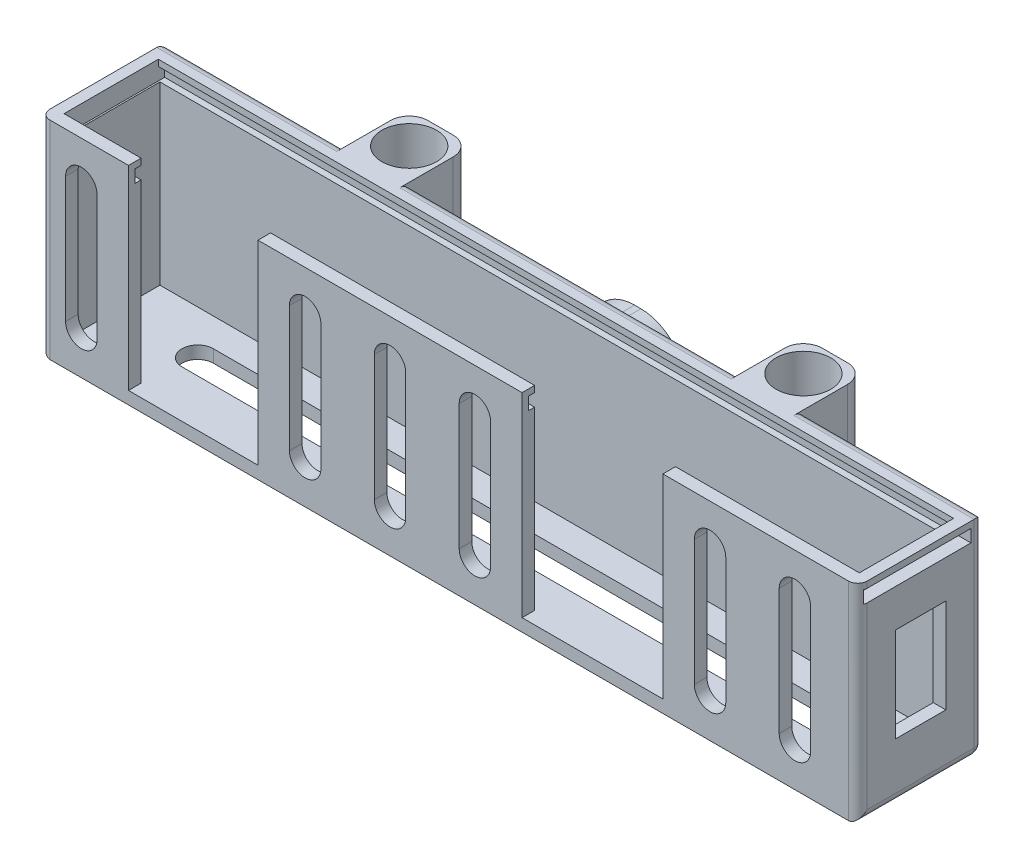
SolidWorks part; units mm, degrees
ref_plane "Plano frontal" through (0, 0, 0) normal (0, 0, 1) x (1, 0, 0)
ref_plane "Plano superior" through (0, 0, 0) normal (0, 1, 0) x (1, 0, 0)
ref_plane "Plano direito" through (0, 0, 0) normal (1, 0, 0) x (0, 0, -1)
sketch "Esboço1" plane through (0, 0, 0) normal (0, 0, 1) x (1, 0, 0)
  line L1 (-65, -16.5) -> (65, -16.5)
  line L2 (-65, -16.5) -> (-65, 16.5)
  line L3 (-65, 16.5) -> (65, 16.5)
  line L4 (65, -16.5) -> (65, 16.5)
  line L5 (-65, -16.5) -> (65, 16.5) construction
  line L6 (-65, 16.5) -> (65, -16.5) construction
  point P0 (0, 0)
  dimension "D1" = 130
  dimension "D2" = 33
extrude "Ressalto-extrusão1" add sketch "Esboço1" along normal blind 3
sketch "Esboço2" plane through (0, 0, 3) normal (0, 0, 1) x (1, 0, 0)
  line L1 (-63, -14.5) -> (63, -14.5)
  line L2 (-63, -14.5) -> (-63, 14.5)
  line L3 (-63, 14.5) -> (63, 14.5)
  line L4 (63, -14.5) -> (63, 14.5)
  line L5 (-63, -14.5) -> (63, 14.5) construction
  line L6 (-63, 14.5) -> (63, -14.5) construction
  point P0 (0, 0)
  dimension "D1" = 126
  dimension "D2" = 29
extrude "Extrusão-Fina1" add sketch "Esboço2" along normal blind 17 thin thin type one direction wall 2
sketch "Esboço3" plane through (0, 16.5, 0) normal (0, 1, 0) x (1, 0, 0)
  line L0 (0, 0) -> (0, -20) construction
  line L1 (65, -20) -> (-65, -20) construction
  line L2 (-63.25, -3) -> (63.25, -3)
  line L8 (63.25, -3) -> (63.25, -18)
  line L9 (65, 0) -> (-65, 0) construction
  line L10 (63.25, -18) -> (-63.25, -18)
  line L11 (-63.25, -18) -> (-63.25, -3)
  line L13 (-65, -20) -> (-65, 0) construction
  dimension "D1" = 3
  dimension "D2" = 126.5
  dimension "D3" = 1.75
  dimension "D4" = 15
extrude "Corte-extrusão1" cut sketch "Esboço3" against normal up to surface (2 mm away) up to face at (0, 14.5, 11.5)
sketch "Esboço4" plane through (65, 0, 0) normal (1, 0, 0) x (0, 0, -1)
  line L0 (0, 0) -> (-20, 0) construction
  line L1 (-20, -16.5) -> (-20, 16.5) construction
  line L2 (0, -16.5) -> (0, 16.5) construction
  line L3 (-14, -7.5) -> (-6, -7.5)
  line L4 (-14, -7.5) -> (-14, 7.5)
  line L5 (-14, 7.5) -> (-6, 7.5)
  line L6 (-6, -7.5) -> (-6, 7.5)
  line L7 (-14, -7.5) -> (-6, 7.5) construction
  line L8 (-14, 7.5) -> (-6, -7.5) construction
  point P5 (-10, 0)
  dimension "D1" = 8
  dimension "D2" = 15
  dimension "D3" = 6
extrude "Corte-extrusão2" cut sketch "Esboço4" against normal up to surface (2 mm away) up to face at (63, 2.9, 12.8)
sketch "Esboço7" plane through (0, -14.5, 0) normal (0, 1, 0) x (1, 0, 0)
  line L0 (-63, -20) -> (63, -20) construction
  line L1 (-30.4, -20) -> (11.6, -20)
  line L2 (-30.4, -20) -> (-30.4, -18)
  line L3 (-30.4, -18) -> (11.6, -18)
  line L4 (11.6, -20) -> (11.6, -18)
  line L7 (-63, -20) -> (-63, -3) construction
  line L9 (-63, -20) -> (-51, -20)
  line L10 (-63, -20) -> (-63, -18)
  line L11 (-63, -18) -> (-51, -18)
  line L12 (-51, -20) -> (-51, -18)
  line L13 (63, -20) -> (34, -20)
  line L14 (63, -20) -> (63, -18)
  line L15 (63, -18) -> (34, -18)
  line L16 (34, -20) -> (34, -18)
  dimension "D1" = 2
  dimension "D2" = 32.6
  dimension "D3" = 42
  dimension "D4" = 2
  dimension "D5" = 12
  dimension "D6" = 29
  dimension "D7" = 2
extrude "Ressalto-extrusão2" add sketch "Esboço7" along normal up to surface (29 mm away) up to face at (0, 14.5, 19)
sketch "Esboço8" plane through (0, 16.5, 0) normal (0, 1, 0) x (1, 0, 0)
  line L0 (65, -20) -> (-65, -20) construction
  line L1 (-51, -20) -> (-51, -18) construction
  line L2 (11.6, -20) -> (11.6, -18) construction
  line L3 (-51, -20) -> (-30.4, -20)
  line L4 (-51, -20) -> (-51, -18)
  line L5 (-51, -18) -> (-30.4, -18)
  line L6 (-30.4, -20) -> (-30.4, -18)
  line L7 (-63.25, -18) -> (63.25, -18) construction
  line L8 (11.6, -20) -> (34, -20)
  line L9 (11.6, -20) -> (11.6, -18)
  line L10 (11.6, -18) -> (34, -18)
  line L11 (34, -20) -> (34, -18)
  dimension "D1" = 20.6
  dimension "D2" = 22.4
extrude "Corte-extrusão4" cut sketch "Esboço8" against normal up to surface (2 mm away) up to face at (22.8, 14.5, 19)
sketch "Esboço5" plane through (65, 0, 0) normal (1, 0, 0) x (0, 0, -1)
  line L0 (0, 0) -> (-20, 0) construction
  line L1 (-20, -16.5) -> (-20, 16.5) construction
  line L2 (-10, 0) -> (-10, 16.5) construction
  line L3 (-20, 16.5) -> (0, 16.5) construction
  line L4 (0, -16.5) -> (0, 16.5) construction
  line L5 (-19, 15.5) -> (-2, 15.5)
  line L6 (-19, 15.5) -> (-19, 13.5)
  line L7 (-19, 13.5) -> (-2, 13.5)
  line L8 (-2, 15.5) -> (-2, 13.5)
  line L9 (-19, 15.5) -> (-2, 13.5) construction
  line L10 (-19, 13.5) -> (-2, 15.5) construction
  point P9 (-10.5, 14.5)
  dimension "D1" = 17
  dimension "D2" = 2
  dimension "D3" = 1
  dimension "D4" = 2
extrude "Corte-extrusão3" cut sketch "Esboço5" against normal up to surface (128.25 mm away) up to face at (-63.25, 15.5, 10.5)
sketch "Esboço9" plane through (0, 0, 20) normal (0, 0, 1) x (1, 0, 0)
  line L0 (-65, 0) -> (65, 0) construction
  line L1 (-65, 16.5) -> (-65, -16.5) construction
  line L2 (65, -16.5) -> (65, 16.5) construction
  line L3 (-58.5, -10) -> (-58.5, 10) construction
  line L4 (-61, -10) -> (-61, 10)
  line L5 (-56, -10) -> (-56, 10)
  line L6 (-22.9, -10) -> (-22.9, 10) construction
  line L7 (-25.4, -10) -> (-25.4, 10)
  line L8 (-20.4, -10) -> (-20.4, 10)
  line L9 (-9.4, -10) -> (-9.4, 10) construction
  line L10 (-11.9, -10) -> (-11.9, 10)
  line L11 (-6.9, -10) -> (-6.9, 10)
  line L12 (4.1, -10) -> (4.1, 10) construction
  line L13 (1.6, -10) -> (1.6, 10)
  line L14 (6.6, -10) -> (6.6, 10)
  line L15 (-30.4, 16.5) -> (-30.4, -14.5) construction
  line L16 (11.6, 16.5) -> (11.6, -14.5) construction
  line L17 (41.5, -10) -> (41.5, 10) construction
  line L18 (39, -10) -> (39, 10)
  line L19 (44, -10) -> (44, 10)
  line L20 (55, -10) -> (55, 10) construction
  line L21 (52.5, -10) -> (52.5, 10)
  line L22 (57.5, -10) -> (57.5, 10)
  line L23 (34, 16.5) -> (34, -14.5) construction
  arc A0 (-61, -10) -> (-56, -10) centre (-58.5, -10) ccw
  arc A1 (-56, 10) -> (-61, 10) centre (-58.5, 10) ccw
  arc A2 (-25.4, -10) -> (-20.4, -10) centre (-22.9, -10) ccw
  arc A3 (-20.4, 10) -> (-25.4, 10) centre (-22.9, 10) ccw
  arc A4 (-11.9, -10) -> (-6.9, -10) centre (-9.4, -10) ccw
  arc A5 (-6.9, 10) -> (-11.9, 10) centre (-9.4, 10) ccw
  arc A6 (1.6, -10) -> (6.6, -10) centre (4.1, -10) ccw
  arc A7 (6.6, 10) -> (1.6, 10) centre (4.1, 10) ccw
  arc A8 (39, -10) -> (44, -10) centre (41.5, -10) ccw
  arc A9 (44, 10) -> (39, 10) centre (41.5, 10) ccw
  arc A10 (52.5, -10) -> (57.5, -10) centre (55, -10) ccw
  arc A11 (57.5, 10) -> (52.5, 10) centre (55, 10) ccw
  point P8 (-58.5, 0)
  point P15 (-22.9, 0)
  point P22 (-9.4, 0)
  point P28 (4.1, 0)
  point P40 (41.5, 0)
  point P46 (55, 0)
  dimension "D1" = 20
  dimension "D2" = 5
  dimension "D3" = 4
  dimension "D4" = 5
  dimension "D5" = 8.5
  dimension "D6" = 5
  dimension "D7" = 5
  dimension "D8" = 8.5
extrude "Corte-extrusão5" cut sketch "Esboço9" against normal up to surface (2 mm away) up to face at (-9.4, -0.5, 18)
sketch "Esboço10" plane through (0, -16.5, 0) normal (0, -1, 0) x (1, 0, 0)
  line L0 (0, 0) -> (0, 20) construction
  line L1 (-65, 0) -> (65, 0) construction
  line L2 (-65, 20) -> (65, 20) construction
  line L3 (-50, 10) -> (50, 10) construction
  line L4 (-50, 12.5) -> (50, 12.5)
  line L5 (-50, 7.5) -> (50, 7.5)
  arc A0 (-50, 12.5) -> (-50, 7.5) centre (-50, 10) ccw
  arc A1 (50, 7.5) -> (50, 12.5) centre (50, 10) ccw
  point P8 (0, 10)
  dimension "D1" = 100
  dimension "D2" = 5
extrude "Corte-extrusão6" cut sketch "Esboço10" against normal up to surface (2 mm away) up to face at (-5.9667, -14.5, 16.1667)
sketch "Esboço11" plane through (0, 0, 0) normal (0, 0, -1) x (-1, 0, 0)
  line L0 (65, 0) -> (-65, 0) construction
  line L1 (65, 16.5) -> (65, -16.5) construction
  line L2 (-65, -16.5) -> (-65, 16.5) construction
  line L3 (0, -16.5) -> (0, 16.5) construction
  line L4 (-36.35, -16.5) -> (-26.35, -16.5)
  line L5 (-36.35, -16.5) -> (-36.35, 16.5)
  line L6 (-36.35, 16.5) -> (-26.35, 16.5)
  line L7 (-26.35, -16.5) -> (-26.35, 16.5)
  line L8 (-36.35, -16.5) -> (-26.35, 16.5) construction
  line L9 (-36.35, 16.5) -> (-26.35, -16.5) construction
  line L10 (65, -16.5) -> (-65, -16.5) construction
  line L11 (-65, 16.5) -> (65, 16.5) construction
  line L12 (36.35, 16.5) -> (26.35, 16.5)
  line L13 (26.35, -16.5) -> (26.35, 16.5)
  line L14 (36.35, -16.5) -> (26.35, -16.5)
  line L15 (36.35, -16.5) -> (36.35, 16.5)
  point P6 (-31.35, 0)
  dimension "D1" = 26.35
  dimension "D2" = 10
  dimension "D3" = 33
extrude "Ressalto-extrusão3" add sketch "Esboço11" along normal blind 10
sketch "Esboço12" plane through (0, -16.5, 0) normal (0, -1, 0) x (1, 0, 0)
  line L0 (-36.35, 0) -> (-26.35, 0) construction
  line L1 (-31.35, 0) -> (-31.35, -10) construction
  line L2 (-26.35, -10) -> (-36.35, -10) construction
  line L3 (0, 0) -> (0, 7.5) construction
  line L4 (-50, 7.5) -> (50, 7.5) construction
  circle A0 centre (-31.35, -5) radius 4.35
  circle A1 centre (31.35, -5) radius 4.35
  dimension "D1" = 8.7
extrude "Corte-extrusão7" cut sketch "Esboço12" against normal through all
sketch "Esboço13" plane through (0, 0, 0) normal (0, 0, -1) x (-1, 0, 0)
  line L1 (-7.5, -7.5) -> (7.5, -7.5)
  line L2 (-7.5, -7.5) -> (-7.5, 7.5)
  line L3 (-7.5, 7.5) -> (7.5, 7.5)
  line L4 (7.5, -7.5) -> (7.5, 7.5)
  line L5 (-7.5, -7.5) -> (7.5, 7.5) construction
  line L6 (-7.5, 7.5) -> (7.5, -7.5) construction
  point P0 (0, 0)
  dimension "D1" = 15
  dimension "D2" = 15
extrude "Ressalto-extrusão4" add sketch "Esboço13" along normal blind 10
fillet "Filete1" radius 7 4 edges at (7.5, 7.5, -5) (7.5, -7.5, -5) (-7.5, 7.5, -5) (-7.5, -7.5, -5)
fillet "Filete2" radius 3 4 edges at (36.35, 0, -10) (26.35, 0, -10) (-26.35, 0, -10) (-36.35, 0, -10)
fillet "Filete3" radius 1.5 12 edges at (50.675, 16.5, 0) (0, 16.5, 0) (-50.675, 16.5, 0) (65, 0, 0) (65, -16.5, 10) (65, 0, 20) (-65, -16.5, 10) (-65, 0, 20) (50.675, -16.5, 0) (0, -16.5, 0) (-50.675, -16.5, 0) (-65, 0, 0)
